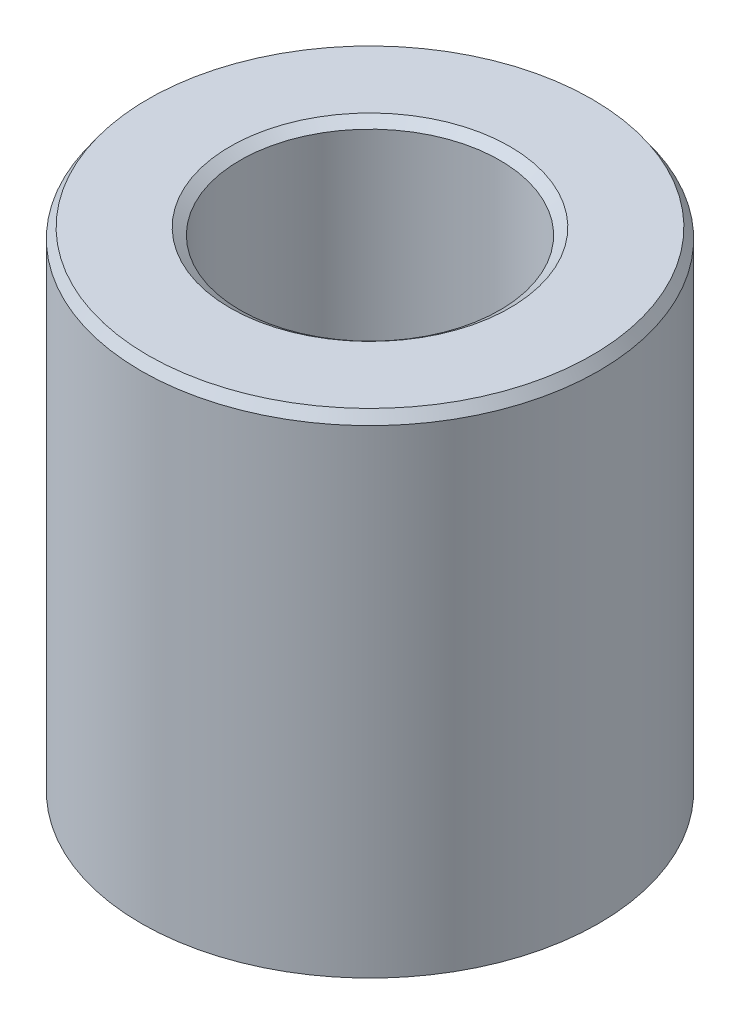
SolidWorks part; units mm, degrees
ref_plane "Front Plane" through (0, 0, 0) normal (0, 0, 1) x (1, 0, 0)
ref_plane "Top Plane" through (0, 0, 0) normal (0, 1, 0) x (1, 0, 0)
ref_plane "Right Plane" through (0, 0, 0) normal (1, 0, 0) x (0, 0, -1)
sketch "Sketch1" plane through (0, 0, 0) normal (0, 1, 0) x (1, 0, 0)
  circle A0 centre (0, 0) radius 60
  dimension "SLEEVE_OD" = 120
extrude "Boss-Extrude1" add sketch "Sketch1" along normal blind 129.8616
sketch "Sketch2" plane through (0, 0, 0) normal (0, 1, 0) x (1, 0, 0)
  circle A0 centre (0, 0) radius 34.0437
  dimension "BORE_D" = 68.0875
extrude "Cut-Extrude1" cut sketch "Sketch2" along normal through all
chamfer "Chamfer1" distance 2.6285 angle 34.569 4 edges at (0, 129.8616, 34.0437) (0, 0, 34.0437) (0, 0, 60) (0, 129.8616, 60) first distance on face at (0, 129.8616, 34.0437) first distance on face at (0, 0, 34.0437) first distance on face at (0, 129.8616, 60)
